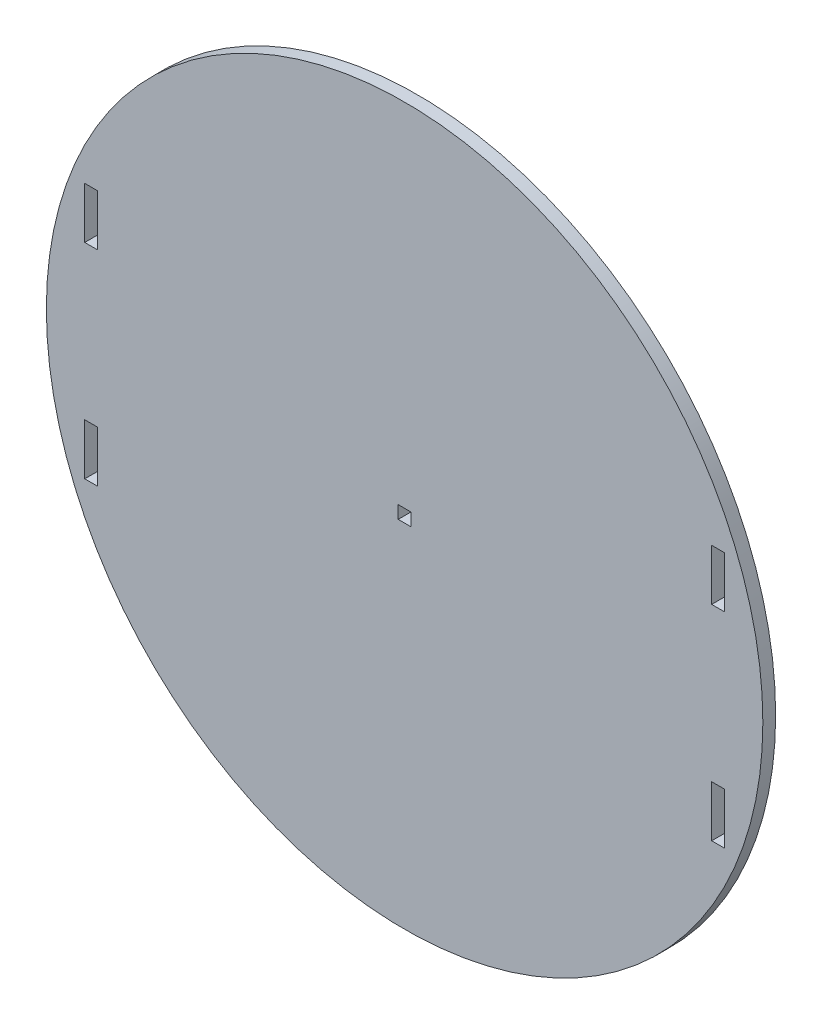
SolidWorks part; units mm, degrees
ref_plane "Front Plane" through (0, 0, 0) normal (0, 0, 1) x (1, 0, 0)
ref_plane "Top Plane" through (0, 0, 0) normal (0, 1, 0) x (1, 0, 0)
ref_plane "Right Plane" through (0, 0, 0) normal (1, 0, 0) x (0, 0, -1)
sketch "Sketch1" plane through (0, 0, 0) normal (0, 0, 1) x (1, 0, 0)
  line L0 (79.375, 31.7348) -> (76.2, 31.7348)
  line L1 (-1.5875, -1.5875) -> (1.5875, -1.5875)
  line L2 (-1.5875, -1.5875) -> (-1.5875, 1.5875)
  line L3 (-1.5875, 1.5875) -> (1.5875, 1.5875)
  line L4 (1.5875, -1.5875) -> (1.5875, 1.5875)
  line L5 (-1.5875, -1.5875) -> (1.5875, 1.5875) construction
  line L6 (-1.5875, 1.5875) -> (1.5875, -1.5875) construction
  line L7 (79.375, 31.7348) -> (79.375, 19.0348)
  line L8 (76.2, 31.7348) -> (76.2, 19.0348)
  line L9 (79.375, 19.0348) -> (76.2, 19.0348)
  line L10 (79.375, -19.0652) -> (76.2, -19.0652)
  line L11 (79.375, -19.0652) -> (79.375, -31.7652)
  line L12 (76.2, -19.0652) -> (76.2, -31.7652)
  line L13 (79.375, -31.7652) -> (76.2, -31.7652)
  line L14 (79.375, -31.7652) -> (76.2, -31.7652) construction
  line L15 (79.375, 19.0348) -> (76.2, 19.0348) construction
  line L16 (0, -1000) -> (0, 49000) construction
  line L17 (-79.375, -31.7652) -> (-76.2, -31.7652)
  line L18 (-76.2, -19.0652) -> (-76.2, -31.7652)
  line L19 (-79.375, -19.0652) -> (-79.375, -31.7652)
  line L20 (-79.375, -19.0652) -> (-76.2, -19.0652)
  line L21 (-79.375, 19.0348) -> (-76.2, 19.0348)
  line L22 (-76.2, 31.7348) -> (-76.2, 19.0348)
  line L23 (-79.375, 31.7348) -> (-79.375, 19.0348)
  line L24 (-79.375, 31.7348) -> (-76.2, 31.7348)
  circle A0 centre (0, 0) radius 88.9
  dimension "D1" = 177.8
  dimension "D2" = 3.175
  dimension "D3" = 3.175
extrude "Boss-Extrude1" add sketch "Sketch1" along normal blind 3.175
